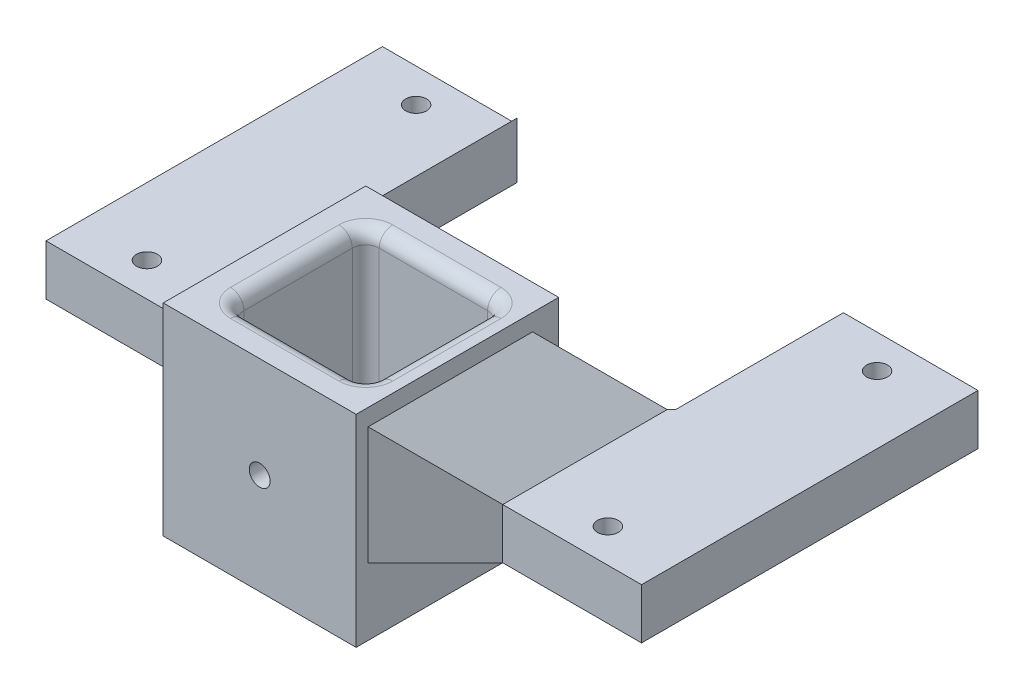
SolidWorks part; units mm, degrees
ref_plane "Front Plane" through (0, 0, 0) normal (0, 0, 1) x (1, 0, 0)
ref_plane "Top Plane" through (0, 0, 0) normal (0, 1, 0) x (1, 0, 0)
ref_plane "Right Plane" through (0, 0, 0) normal (1, 0, 0) x (0, 0, -1)
sketch "Sketch1" plane through (0, 0, 0) normal (0, 1, 0) x (1, 0, 0)
  line L0 (0, 0) -> (-20.1, 0) construction
  line L1 (0, 0) -> (80, 0)
  line L2 (0, 0) -> (0, 20.1)
  line L3 (0, 20.1) -> (80, 20.1)
  line L4 (80, 0) -> (80, 20.1)
  line L8 (-20.1, 20.1) -> (-20.1, 0)
  line L9 (-20.1, 20.1) -> (0, 0) construction
  line L10 (-20.1, 20.1) -> (0, 20.1)
  line L11 (-20.1, 20.1) -> (-20.1, 0)
  line L12 (-20.1, 0) -> (0, 0)
  line L13 (0, 20.1) -> (0, 0)
  line L14 (-20.1, 0) -> (0, 20.1) construction
  line L15 (-20.1, 0) -> (-20.1, -80)
  line L16 (0, 0) -> (0, -80)
  line L17 (-20.1, -80) -> (0, -80)
  line L18 (-20.1, 0) -> (0, 0)
  line L19 (-20.1, 20.1) -> (-100.1, 20.1)
  line L20 (-20.1, 0) -> (-100.1, 0)
  line L21 (-100.1, 20.1) -> (-100.1, 0)
  line L22 (-20.1, 20.1) -> (-20.1, 0)
  line L23 (0, 20.1) -> (0, 100.1)
  line L24 (-20.1, 20.1) -> (-20.1, 100.1)
  line L25 (0, 100.1) -> (-20.1, 100.1)
  line L26 (0, 20.1) -> (-20.1, 20.1)
  circle A5 centre (74, 14.1) radius 1.55
  circle A7 centre (74, 6) radius 1.55
  circle A9 centre (-6, -74) radius 1.55
  circle A11 centre (-14.1, -74) radius 1.55
  circle A13 centre (-94.1, 6) radius 1.55
  circle A15 centre (-94.1, 14.1) radius 1.55
  circle A17 centre (-14.1, 94.1) radius 1.55
  circle A19 centre (-6, 94.1) radius 1.55
  point P11 (-10.05, 10.05)
  point P56 (-10.05, 10.05)
  dimension "D4" = 4
  dimension "D11" = 3.1
  dimension "D13" = 3.1
  dimension "D3" = 20.1
  dimension "D5" = 80
  dimension "D24" = 6
  dimension "D25" = 6
  dimension "D26" = 6
  dimension "D27" = 6
sketch "Sketch2" plane through (0, 0, 0) normal (0, 1, 0) x (1, 0, 0)
  line L1 (-54.3, 56.78) -> (-34.3, 56.78)
  line L2 (-54.3, 56.78) -> (-54.3, 6.78)
  line L3 (-54.3, 6.78) -> (-40, 6.78)
  line L9 (14.2, 56.78) -> (34.2, 56.78)
  line L12 (34.2, 56.78) -> (34.2, 6.78)
  line L16 (-20.1, 20.1) -> (0, 20.1) construction
  line L17 (-40, 6.78) -> (34.2, 6.78)
  line L18 (-44.3, 51.78) -> (24.2, 51.78) construction
  line L19 (24.2, 51.78) -> (24.2, 11.78) construction
  line L20 (-10.05, 51.78) -> (-10.05, 20.1) construction
  line L22 (-40, 40) -> (-40, 0) construction
  line L23 (-54.3, 51.78) -> (-34.3, 51.78) construction
  line L25 (14.2, 51.78) -> (34.2, 51.78) construction
  line L26 (-34.3, 31.85) -> (-22.55, 20.1)
  line L27 (14.2, 31.85) -> (2.45, 20.1)
  line L28 (14.2, 56.78) -> (14.2, 31.85)
  line L29 (-34.3, 56.78) -> (-34.3, 31.85)
  line L30 (-22.55, 20.1) -> (2.45, 20.1)
  line L33 (-20.1, 20.1) -> (0, 20.1)
  line L34 (-20.1, 20.1) -> (-20.1, 0)
  line L35 (-20.1, 0) -> (0, 0)
  line L36 (0, 20.1) -> (0, 0)
  line L37 (-25.1, 25.1) -> (3.5699, 25.1)
  line L38 (-25.1, 25.1) -> (-25.1, -5)
  line L39 (-25.1, -5) -> (3.5699, -5)
  line L40 (3.5699, 25.1) -> (3.5699, -5)
  circle A0 centre (-44.3, 51.78) radius 1.55
  circle A1 centre (24.2, 51.78) radius 1.55
  circle A2 centre (-44.3, 11.78) radius 1.55
  circle A3 centre (24.2, 11.78) radius 1.55
  point P4 (-10.05, 20.1)
  point P16 (24.2, 51.78)
  point P24 (-44.3, 51.78)
  dimension "D4" = 3.1
  dimension "D5" = 3.1
  dimension "D9" = 3.1
  dimension "D13" = 3.1
  dimension "D1" = 68.5
  dimension "D2" = 20
  dimension "D3" = 5
  dimension "D6" = 31.68
  dimension "D7" = 20
  dimension "D8" = 40
  dimension "D10" = 5
  dimension "D11" = 5
  dimension "D12" = 10
  dimension "D14" = 5
  dimension "D15" = 45
  dimension "D16" = 45
  dimension "D17" = 25
  dimension "D18" = 5
  dimension "D19" = 5
  dimension "D20" = 5
  dimension "D21" = 3.5699
extrude "Boss-Extrude3" add sketch "Sketch2" along normal blind 7.5 from offset 180 contours L38 L26 L29 L1 L2 L3 L17 A2 A0 | L27 L40 L17 L12 L9 L28 A3 A1 | L26 L38 L17 L34 L30 | L40 L37 L38 L26 L30 L27 | L40 L27 L30 L36 L17 | L40 L17 L36 L35 L34 L38 L39 region at (-42.0118, 0, -29.4376) region at (-10.5135, 0, -22.648) region at (-22.6768, 0, -13.7896) region at (-11.2488, 0, 0.8012) region at (1.8033, 0, -13.5315) region at (21.5922, 0, -29.1642)
extrude "Boss-Extrude4" add sketch "Sketch2<3>" along normal blind 30 from offset 170 contours L26 L38 L17 L34 L30 | L40 L37 L38 L26 L30 L27 | L40 L27 L30 L36 L17 | L40 L17 L36 L35 L34 L38 L39 region at (-10.5135, 0, -22.648) region at (-22.6768, 0, -13.7896) region at (-11.2488, 0, 0.8012) region at (1.8033, 0, -13.5315)
sketch "Sketch2<3>" plane through (0, 0, 0) normal (0, 1, 0) x (1, 0, 0) same geometry as "Sketch2"
chamfer "Chamfer1" distance 10 angle 45 2 edges at (-25.1, 187.5, -14.715) (3.5699, 187.5, -14)
chamfer "Chamfer2" distance 10 angle 45 2 edges at (-25.1, 188.75, -6.78) (3.5699, 188.75, -6.78)
sketch "Sketch3" plane through (0, 0, -25.1) normal (0, 0, -1) x (-1, 0, 0)
  line L0 (-3.5699, 200) -> (25.1, 170) construction
  circle A0 centre (10.765, 185) radius 1.55
  point P6 (0, 0)
  point P7 (10.765, 185)
  dimension "D1" = 3.1
extrude "Cut-Extrude1" cut sketch "Sketch3" against normal blind 43
fillet "Fillet1" radius 2 12 edges at (-10.05, 200, -20.1) (-10.05, 200, 0) (-10.05, 170, 0) (-10.05, 170, -20.1) (-20.1, 200, -10.05) (-20.1, 185, -20.1) (-20.1, 170, -10.05) (-20.1, 185, 0) (0, 200, -10.05) (0, 185, 0) (0, 170, -10.05) (0, 185, -20.1)
